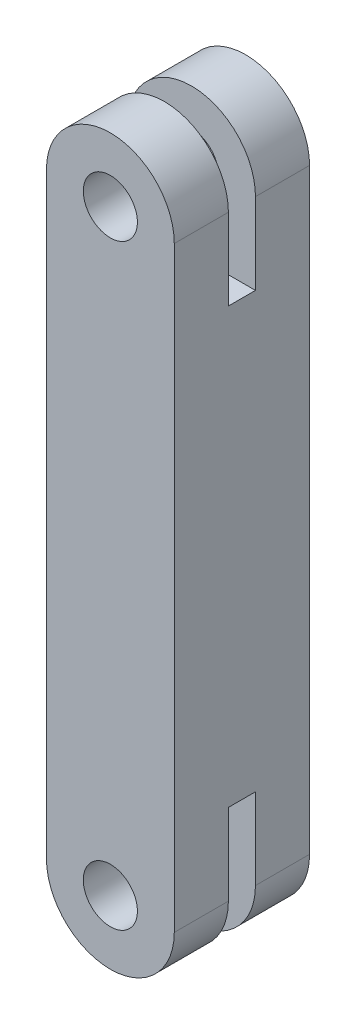
SolidWorks part; units mm, degrees
ref_plane "Front Plane" through (0, 0, 0) normal (0, 0, 1) x (1, 0, 0)
ref_plane "Top Plane" through (0, 0, 0) normal (0, 1, 0) x (1, 0, 0)
ref_plane "Right Plane" through (0, 0, 0) normal (1, 0, 0) x (0, 0, -1)
sketch "Sketch1" plane through (0, 0, 0) normal (0, 0, 1) x (1, 0, 0)
  line L0 (-7.5, 70) -> (-7.5, 0)
  line L2 (7.5, 0) -> (7.5, 70)
  arc A0 (-7.5, 0) -> (7.5, 0) centre (0, 0) ccw
  arc A1 (7.5, 70) -> (-7.5, 70) centre (0, 70) ccw
  circle A2 centre (0, 70) radius 3.175
  circle A3 centre (0, 0) radius 3.175
  dimension "D2" = 15
  dimension "D3" = 6.35
  dimension "D1" = 70
extrude "Boss-Extrude1" add sketch "Sketch1" along normal mid plane 15.875
sketch "Sketch2" plane through (0, 0, 0) normal (0, 0, 1) x (1, 0, 0)
  line L0 (-7.5, 70) -> (-7.5, 0) construction
  line L1 (-7.5, 9.525) -> (7.5, 9.525)
  line L2 (-7.5, 9.525) -> (-7.5, -7.5)
  line L3 (-7.5, -7.5) -> (7.5, -7.5)
  line L4 (7.5, 9.525) -> (7.5, -7.5)
  line L5 (7.5, 0) -> (7.5, 70) construction
  line L7 (-7.5, 60.475) -> (7.5, 60.475)
  line L8 (-7.5, 60.475) -> (-7.5, 77.5)
  line L9 (-7.5, 77.5) -> (7.5, 77.5)
  line L10 (7.5, 60.475) -> (7.5, 77.5)
  arc A0 (-7.5, 0) -> (7.5, 0) centre (0, 0) ccw construction
  arc A1 (7.5, 70) -> (-7.5, 70) centre (0, 70) ccw construction
  dimension "D1" = 9.525
extrude "Cut-Extrude1" cut sketch "Sketch2" against normal mid plane 3.175
